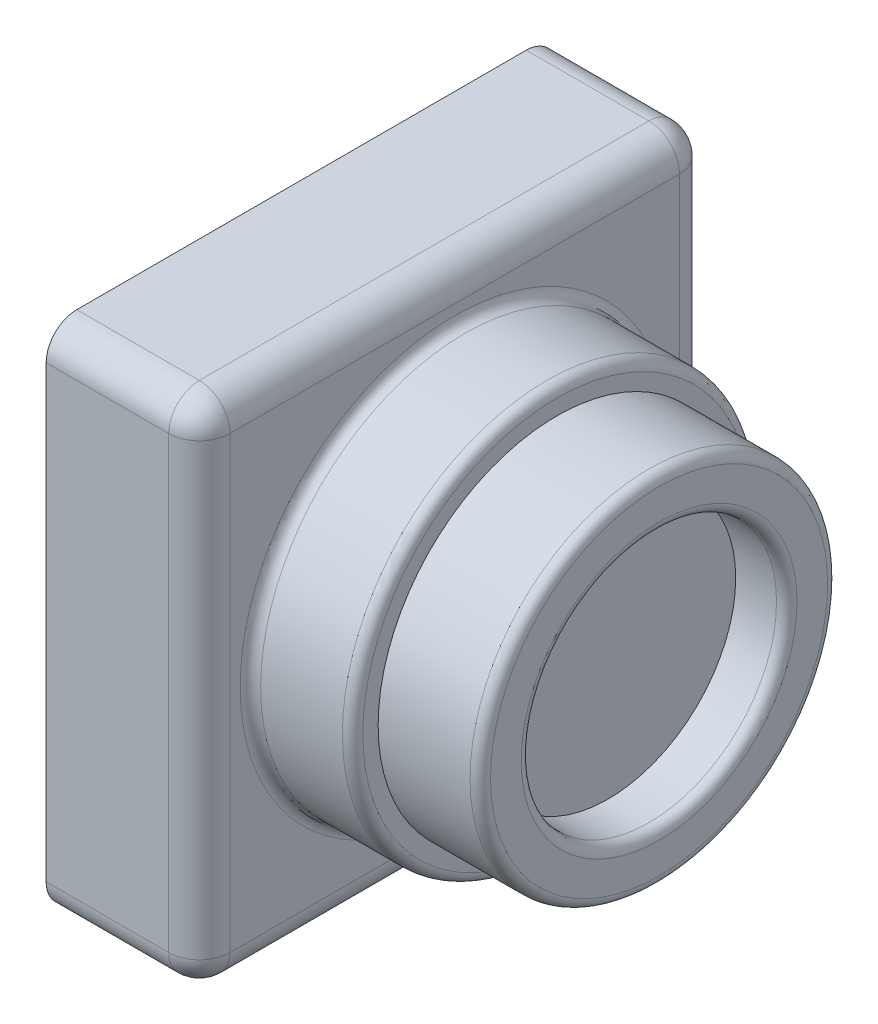
SolidWorks part; units mm, degrees
ref_plane "Front Plane" through (0, 0, 0) normal (0, 0, 1) x (1, 0, 0)
ref_plane "Top Plane" through (0, 0, 0) normal (0, 1, 0) x (1, 0, 0)
ref_plane "Right Plane" through (0, 0, 0) normal (1, 0, 0) x (0, 0, -1)
sketch "Sketch1" plane through (0, 0, 0) normal (1, 0, 0) x (0, 0, -1)
  line L1 (-25, 25) -> (25, 25)
  line L2 (-25, 25) -> (-25, -25)
  line L3 (-25, -25) -> (25, -25)
  line L4 (25, 25) -> (25, -25)
  line L5 (-25, 25) -> (25, -25) construction
  line L6 (-25, -25) -> (25, 25) construction
  point P0 (0, 0)
  dimension "D1" = 50
  dimension "D2" = 50
extrude "Boss-Extrude1" add sketch "Sketch1" along normal blind 15
sketch "Sketch2" plane through (15, 0, 0) normal (1, 0, 0) x (0, 0, -1)
  circle A0 centre (0, 0) radius 20
  dimension "D1" = 40
extrude "Boss-Extrude2" add sketch "Sketch2" along normal blind 20
sketch "Sketch3" plane through (35, 0, 0) normal (1, 0, 0) x (0, 0, -1)
  circle A0 centre (0, 0) radius 20
  circle A1 centre (0, 0) radius 17.5
  circle A2 centre (0, 0) radius 12.5
  circle M3 centre (0, 0) radius 20
  dimension "D1" = 40
  dimension "D2" = 35
  dimension "D3" = 25
extrude "Cut-Extrude1" cut sketch "Sketch3" against normal blind 10 contours A1 M3 | A2 region at (35, 0, 19.4343) region at (35, 0, 0)
sketch "Sketch4" plane through (25, 0, 0) normal (1, 0, 0) x (0, 0, -1)
  circle A0 centre (0, 0) radius 12.5
  dimension "D1" = 25
extrude "Boss-Extrude3" add sketch "Sketch4" along normal blind 5
fillet "Fillet1" radius 1 4 edges at (15, 0, -20) (35, 0, -12.5) (35, 0, -17.5) (25, 0, -20)
fillet "Fillet2" radius 3 4 edges at (15, -25, 0) (15, 0, -25) (15, 25, 0) (15, 0, 25)
fillet "Fillet3" radius 3 8 edges at (14.1213, -24.1213, 24.1213) (14.1213, -24.1213, -24.1213) (14.1213, 24.1213, -24.1213) (14.1213, 24.1213, 24.1213) (6, -25, 25) (6, -25, -25) (6, 25, -25) (6, 25, 25)
